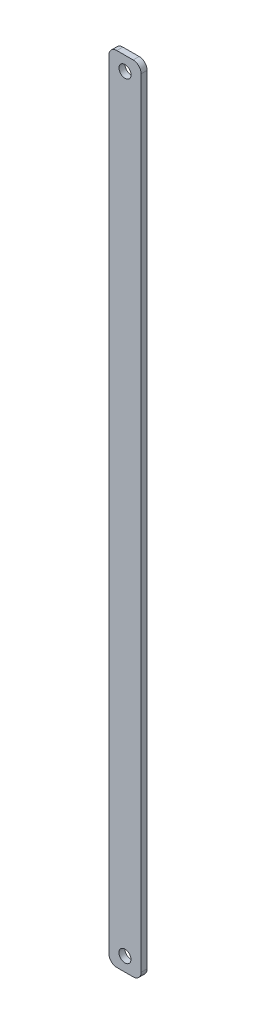
SolidWorks part; units mm, degrees
ref_plane "Front Plane" through (0, 0, 0) normal (0, 0, 1) x (1, 0, 0)
ref_plane "Top Plane" through (0, 0, 0) normal (0, 1, 0) x (1, 0, 0)
ref_plane "Right Plane" through (0, 0, 0) normal (1, 0, 0) x (0, 0, -1)
sketch "Sketch1" plane through (0, 0, 0) normal (0, 1, 0) x (1, 0, 0)
  line L1 (-4.035, -0.75) -> (4.035, -0.75)
  line L2 (-4.035, -0.75) -> (-4.035, 0.75)
  line L3 (-4.035, 0.75) -> (4.035, 0.75)
  line L4 (4.035, -0.75) -> (4.035, 0.75)
  line L5 (-4.035, -0.75) -> (4.035, 0.75) construction
  line L6 (-4.035, 0.75) -> (4.035, -0.75) construction
  point P0 (0, 0)
  dimension "D1" = 8.07
  dimension "D2" = 1.5
extrude "Boss-Extrude1" add sketch "Sketch1" along normal blind 198.5
sketch "Sketch2" plane through (0, 0, 0.75) normal (0, 0, 1) x (1, 0, 0)
  line L0 (-4.035, 198.5) -> (-4.035, 0) construction
  line L1 (-4.035, 198.5) -> (4.035, 198.5) construction
  line L3 (4.035, 198.5) -> (4.035, 0) construction
  circle A0 centre (-0.005, 3.5) radius 1.5
  circle A1 centre (0.005, 195) radius 1.5
  dimension "D2" = 3
  dimension "D4" = 3
  dimension "D1" = 3.5
  dimension "D3" = 4.03
  dimension "D5" = 3.5
  dimension "D6" = 4.03
extrude "Cut-Extrude1" cut sketch "Sketch2" against normal up to surface (1.5 mm away) up to face at (0, 99.25, -0.75)
fillet "Fillet1" radius 2 4 edges at (-4.035, 0, 0) (4.035, 0, 0) (-4.035, 198.5, 0) (4.035, 198.5, 0)
